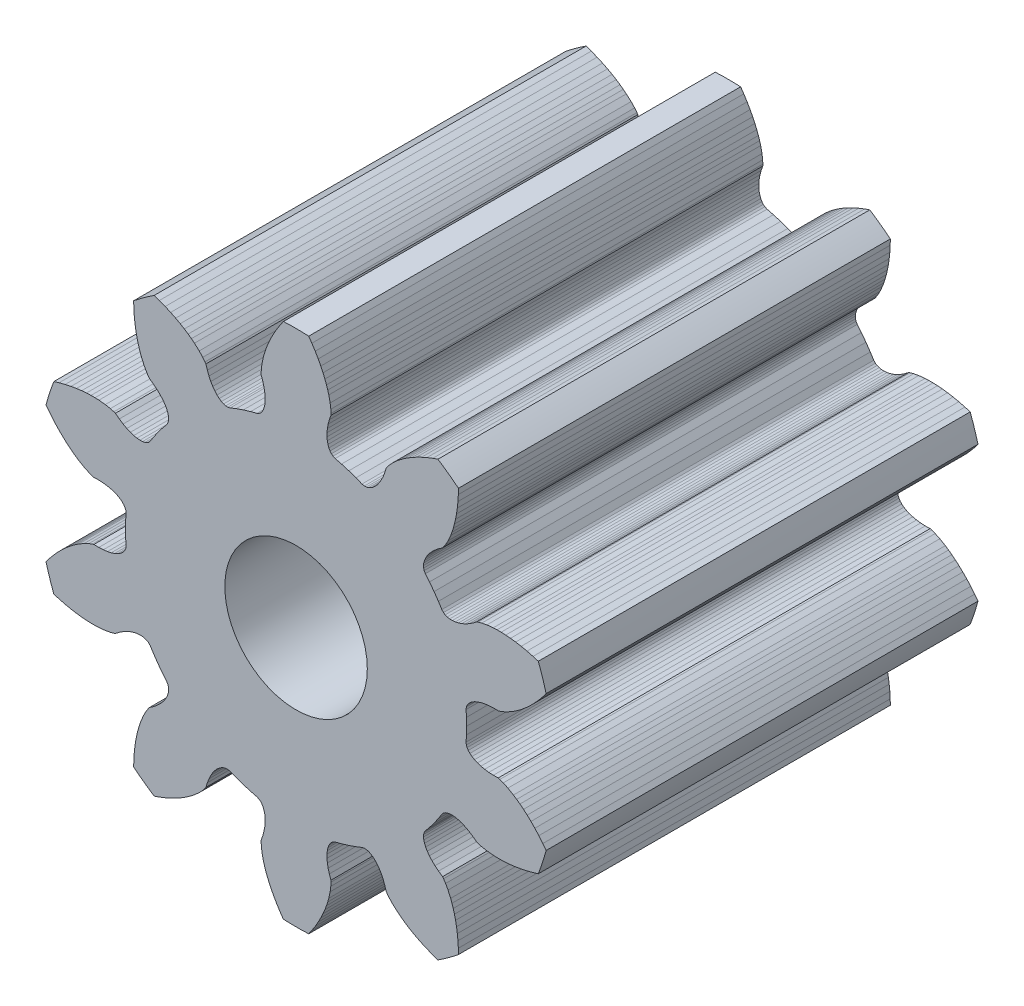
SolidWorks part; units mm, degrees
ref_plane "Front Plane" through (0, 0, 0) normal (0, 0, 1) x (1, 0, 0)
ref_plane "Top Plane" through (0, 0, 0) normal (0, 1, 0) x (1, 0, 0)
ref_plane "Right Plane" through (0, 0, 0) normal (1, 0, 0) x (0, 0, -1)
sketch "Sketch1" plane through (0, 0, 0) normal (0, 0, 1) x (1, 0, 0)
  line L0 (11.2428, -4.5485) -> (11.2517, -4.4039)
  line L1 (11.2517, -4.4039) -> (11.266, -4.2669)
  line L2 (11.266, -4.2669) -> (11.2847, -4.1393)
  line L3 (11.2847, -4.1393) -> (11.3071, -4.0209)
  line L4 (11.3071, -4.0209) -> (11.3325, -3.912)
  line L5 (11.3325, -3.912) -> (11.3608, -3.8103)
  line L6 (11.3608, -3.8103) -> (11.3897, -3.7211)
  line L7 (11.3897, -3.7211) -> (11.4208, -3.6371)
  line L8 (11.4208, -3.6371) -> (11.4807, -3.5016)
  line L9 (11.4807, -3.5016) -> (11.5377, -3.3971)
  line L10 (11.5377, -3.3971) -> (11.5845, -3.3262)
  line L11 (11.5845, -3.3262) -> (11.6076, -3.2964)
  line L12 (11.6076, -3.2964) -> (11.7007, -3.2317)
  line L13 (11.7007, -3.2317) -> (11.7827, -3.1653)
  line L14 (11.7827, -3.1653) -> (11.8533, -3.098)
  line L15 (11.8533, -3.098) -> (11.9128, -3.0308)
  line L16 (11.9128, -3.0308) -> (11.9612, -2.9643)
  line L17 (11.9612, -2.9643) -> (11.9989, -2.8995)
  line L18 (11.9989, -2.8995) -> (12.0259, -2.837)
  line L19 (12.0259, -2.837) -> (12.0426, -2.7776)
  line L20 (12.0426, -2.7776) -> (12.0493, -2.7222)
  line L21 (12.0493, -2.7222) -> (12.0463, -2.6714)
  line L22 (12.0463, -2.6714) -> (12.0342, -2.6259)
  line L23 (12.0342, -2.6259) -> (12.0067, -2.5776)
  line L24 (12.0067, -2.5776) -> (11.9109, -2.4617)
  line L25 (11.9109, -2.4617) -> (11.8044, -2.3217)
  line L26 (11.8044, -2.3217) -> (11.7041, -2.1772)
  line L27 (11.7041, -2.1772) -> (11.6236, -2.0503)
  line L28 (11.6236, -2.0503) -> (11.5861, -2.0092)
  line L29 (11.5861, -2.0092) -> (11.5466, -1.9836)
  line L30 (11.5466, -1.9836) -> (11.4992, -1.9651)
  line L31 (11.4992, -1.9651) -> (11.4444, -1.9543)
  line L32 (11.4444, -1.9543) -> (11.3828, -1.9518)
  line L33 (11.3828, -1.9518) -> (11.315, -1.9582)
  line L34 (11.315, -1.9582) -> (11.2417, -1.974)
  line L35 (11.2417, -1.974) -> (11.1635, -1.9995)
  line L36 (11.1635, -1.9995) -> (11.0812, -2.0353)
  line L37 (11.0812, -2.0353) -> (10.9954, -2.0817)
  line L38 (10.9954, -2.0817) -> (10.907, -2.1391)
  line L39 (10.907, -2.1391) -> (10.8166, -2.2077)
  line L40 (10.8166, -2.2077) -> (10.7811, -2.2204)
  line L41 (10.7811, -2.2204) -> (10.6992, -2.243)
  line L42 (10.6992, -2.243) -> (10.5823, -2.2649)
  line L43 (10.5823, -2.2649) -> (10.4348, -2.2801)
  line L44 (10.4348, -2.2801) -> (10.3453, -2.2837)
  line L45 (10.3453, -2.2837) -> (10.2516, -2.2836)
  line L46 (10.2516, -2.2836) -> (10.1461, -2.2791)
  line L47 (10.1461, -2.2791) -> (10.0348, -2.2696)
  line L48 (10.0348, -2.2696) -> (9.9151, -2.2543)
  line L49 (9.9151, -2.2543) -> (9.7881, -2.2327)
  line L50 (9.7881, -2.2327) -> (9.6533, -2.2039)
  line L51 (9.6533, -2.2039) -> (9.5131, -2.1677)
  line L52 (9.5131, -2.1677) -> (9.3912, -2.1311)
  line L53 (9.2098, -1.5726) -> (9.2868, -1.4714)
  line L54 (9.2868, -1.4714) -> (9.379, -1.3597)
  line L55 (9.379, -1.3597) -> (9.4711, -1.2572)
  line L56 (9.4711, -1.2572) -> (9.5612, -1.165)
  line L57 (9.5612, -1.165) -> (9.649, -1.0823)
  line L58 (9.649, -1.0823) -> (9.7335, -1.0092)
  line L59 (9.7335, -1.0092) -> (9.8162, -0.9435)
  line L60 (9.8162, -0.9435) -> (9.8919, -0.8883)
  line L61 (9.8919, -0.8883) -> (9.9665, -0.8387)
  line L62 (9.9665, -0.8387) -> (10.0947, -0.7642)
  line L63 (10.0947, -0.7642) -> (10.2021, -0.7133)
  line L64 (10.2021, -0.7133) -> (10.2817, -0.6834)
  line L65 (10.2817, -0.6834) -> (10.3179, -0.6728)
  line L66 (10.3179, -0.6728) -> (10.4313, -0.6752)
  line L67 (10.4313, -0.6752) -> (10.5366, -0.6696)
  line L68 (10.5366, -0.6696) -> (10.6333, -0.6568)
  line L69 (10.6333, -0.6568) -> (10.7209, -0.6373)
  line L70 (10.7209, -0.6373) -> (10.7992, -0.612)
  line L71 (10.7992, -0.612) -> (10.8678, -0.5817)
  line L72 (10.8678, -0.5817) -> (10.9263, -0.547)
  line L73 (10.9263, -0.547) -> (10.9747, -0.5088)
  line L74 (10.9747, -0.5088) -> (11.0127, -0.4679)
  line L75 (11.0127, -0.4679) -> (11.0402, -0.4251)
  line L76 (11.0402, -0.4251) -> (11.0571, -0.3811)
  line L77 (11.0571, -0.3811) -> (11.0633, -0.3259)
  line L78 (11.0633, -0.3259) -> (11.0539, -0.1759)
  line L79 (11.0539, -0.1759) -> (11.05, 0)
  line L80 (11.05, 0) -> (11.0539, 0.1759)
  line L81 (11.0539, 0.1759) -> (11.0633, 0.3259)
  line L82 (11.0633, 0.3259) -> (11.0571, 0.3812)
  line L83 (11.0571, 0.3812) -> (11.0402, 0.4251)
  line L84 (11.0402, 0.4251) -> (11.0127, 0.468)
  line L85 (11.0127, 0.468) -> (10.9747, 0.5089)
  line L86 (10.9747, 0.5089) -> (10.9263, 0.5471)
  line L87 (10.9263, 0.5471) -> (10.8678, 0.5817)
  line L88 (10.8678, 0.5817) -> (10.7992, 0.6121)
  line L89 (10.7992, 0.6121) -> (10.7209, 0.6374)
  line L90 (10.7209, 0.6374) -> (10.6333, 0.6568)
  line L91 (10.6333, 0.6568) -> (10.5366, 0.6697)
  line L92 (10.5366, 0.6697) -> (10.4313, 0.6753)
  line L93 (10.4313, 0.6753) -> (10.3179, 0.6729)
  line L94 (10.3179, 0.6729) -> (10.2817, 0.6834)
  line L95 (10.2817, 0.6834) -> (10.2021, 0.7133)
  line L96 (10.2021, 0.7133) -> (10.0947, 0.7643)
  line L97 (10.0947, 0.7643) -> (9.9665, 0.8387)
  line L98 (9.9665, 0.8387) -> (9.8919, 0.8884)
  line L99 (9.8919, 0.8884) -> (9.8162, 0.9436)
  line L100 (9.8162, 0.9436) -> (9.7335, 1.0093)
  line L101 (9.7335, 1.0093) -> (9.649, 1.0824)
  line L102 (9.649, 1.0824) -> (9.5612, 1.165)
  line L103 (9.5612, 1.165) -> (9.4711, 1.2572)
  line L104 (9.4711, 1.2572) -> (9.379, 1.3597)
  line L105 (9.379, 1.3597) -> (9.2868, 1.4714)
  line L106 (9.2868, 1.4714) -> (9.2098, 1.5727)
  line L107 (9.3912, 2.1311) -> (9.5131, 2.1677)
  line L108 (9.5131, 2.1677) -> (9.6533, 2.2039)
  line L109 (9.6533, 2.2039) -> (9.788, 2.2327)
  line L110 (9.788, 2.2327) -> (9.9151, 2.2544)
  line L111 (9.9151, 2.2544) -> (10.0347, 2.2696)
  line L112 (10.0347, 2.2696) -> (10.1461, 2.2791)
  line L113 (10.1461, 2.2791) -> (10.2516, 2.2836)
  line L114 (10.2516, 2.2836) -> (10.3453, 2.2837)
  line L115 (10.3453, 2.2837) -> (10.4348, 2.2801)
  line L116 (10.4348, 2.2801) -> (10.5823, 2.265)
  line L117 (10.5823, 2.265) -> (10.6992, 2.2431)
  line L118 (10.6992, 2.2431) -> (10.7811, 2.2205)
  line L119 (10.7811, 2.2205) -> (10.8166, 2.2078)
  line L120 (10.8166, 2.2078) -> (10.9069, 2.1391)
  line L121 (10.9069, 2.1391) -> (10.9954, 2.0818)
  line L122 (10.9954, 2.0818) -> (11.0812, 2.0353)
  line L123 (11.0812, 2.0353) -> (11.1635, 1.9995)
  line L124 (11.1635, 1.9995) -> (11.2417, 1.974)
  line L125 (11.2417, 1.974) -> (11.315, 1.9583)
  line L126 (11.315, 1.9583) -> (11.3828, 1.9519)
  line L127 (11.3828, 1.9519) -> (11.4444, 1.9543)
  line L128 (11.4444, 1.9543) -> (11.4991, 1.9651)
  line L129 (11.4991, 1.9651) -> (11.5465, 1.9836)
  line L130 (11.5465, 1.9836) -> (11.586, 2.0092)
  line L131 (11.586, 2.0092) -> (11.6235, 2.0503)
  line L132 (11.6235, 2.0503) -> (11.7041, 2.1772)
  line L133 (11.7041, 2.1772) -> (11.8043, 2.3218)
  line L134 (11.8043, 2.3218) -> (11.9109, 2.4618)
  line L135 (11.9109, 2.4618) -> (12.0067, 2.5776)
  line L136 (12.0067, 2.5776) -> (12.0341, 2.626)
  line L137 (12.0341, 2.626) -> (12.0463, 2.6715)
  line L138 (12.0463, 2.6715) -> (12.0492, 2.7223)
  line L139 (12.0492, 2.7223) -> (12.0426, 2.7777)
  line L140 (12.0426, 2.7777) -> (12.0259, 2.837)
  line L141 (12.0259, 2.837) -> (11.9988, 2.8995)
  line L142 (11.9988, 2.8995) -> (11.9612, 2.9643)
  line L143 (11.9612, 2.9643) -> (11.9128, 3.0308)
  line L144 (11.9128, 3.0308) -> (11.8533, 3.0981)
  line L145 (11.8533, 3.0981) -> (11.7826, 3.1653)
  line L146 (11.7826, 3.1653) -> (11.7007, 3.2317)
  line L147 (11.7007, 3.2317) -> (11.6075, 3.2964)
  line L148 (11.6075, 3.2964) -> (11.5845, 3.3262)
  line L149 (11.5845, 3.3262) -> (11.5377, 3.3972)
  line L150 (11.5377, 3.3972) -> (11.4807, 3.5016)
  line L151 (11.4807, 3.5016) -> (11.4208, 3.6372)
  line L152 (11.4208, 3.6372) -> (11.3896, 3.7212)
  line L153 (11.3896, 3.7212) -> (11.3608, 3.8103)
  line L154 (11.3608, 3.8103) -> (11.3325, 3.9121)
  line L155 (11.3325, 3.9121) -> (11.3071, 4.0209)
  line L156 (11.3071, 4.0209) -> (11.2846, 4.1394)
  line L157 (11.2846, 4.1394) -> (11.2659, 4.2669)
  line L158 (11.2659, 4.2669) -> (11.2517, 4.404)
  line L159 (11.2517, 4.404) -> (11.2428, 4.5485)
  line L160 (11.2428, 4.5485) -> (11.2399, 4.6757)
  line L161 (11.715, 5.0209) -> (11.8351, 4.9789)
  line L162 (11.8351, 4.9789) -> (11.9698, 4.9257)
  line L163 (11.9698, 4.9257) -> (12.0958, 4.8698)
  line L164 (12.0958, 4.8698) -> (12.2113, 4.8127)
  line L165 (12.2113, 4.8127) -> (12.3171, 4.7547)
  line L166 (12.3171, 4.7547) -> (12.4127, 4.6969)
  line L167 (12.4127, 4.6969) -> (12.5007, 4.6385)
  line L168 (12.5007, 4.6385) -> (12.5766, 4.5836)
  line L169 (12.5766, 4.5836) -> (12.6469, 4.528)
  line L170 (12.6469, 4.528) -> (12.7573, 4.4291)
  line L171 (12.7573, 4.4291) -> (12.839, 4.3427)
  line L172 (12.839, 4.3427) -> (12.892, 4.2762)
  line L173 (12.892, 4.2762) -> (12.9132, 4.2451)
  line L174 (12.9132, 4.2451) -> (12.946, 4.1364)
  line L175 (12.946, 4.1364) -> (12.9838, 4.038)
  line L176 (12.9838, 4.038) -> (13.0259, 3.9501)
  line L177 (13.0259, 3.9501) -> (13.0715, 3.8727)
  line L178 (13.0715, 3.8727) -> (13.1197, 3.8061)
  line L179 (13.1197, 3.8061) -> (13.1698, 3.7503)
  line L180 (13.1698, 3.7503) -> (13.2209, 3.7053)
  line L181 (13.2209, 3.7053) -> (13.2721, 3.671)
  line L182 (13.2721, 3.671) -> (13.3228, 3.6476)
  line L183 (13.3228, 3.6476) -> (13.372, 3.6347)
  line L184 (13.372, 3.6347) -> (13.419, 3.6322)
  line L185 (13.419, 3.6322) -> (13.4735, 3.6434)
  line L186 (13.4735, 3.6434) -> (13.6133, 3.6987)
  line L187 (13.6133, 3.6987) -> (13.7794, 3.7567)
  line L188 (13.7794, 3.7567) -> (13.9478, 3.8074)
  line L189 (13.9478, 3.8074) -> (14.0934, 3.8448)
  line L190 (14.0934, 3.8448) -> (14.1441, 3.8678)
  line L191 (14.1441, 3.8678) -> (14.1806, 3.8974)
  line L192 (14.1806, 3.8974) -> (14.2129, 3.9368)
  line L193 (14.2129, 3.9368) -> (14.2401, 3.9855)
  line L194 (14.2401, 3.9855) -> (14.2614, 4.0434)
  line L195 (14.2614, 4.0434) -> (14.2763, 4.1098)
  line L196 (14.2763, 4.1098) -> (14.284, 4.1844)
  line L197 (14.284, 4.1844) -> (14.2838, 4.2666)
  line L198 (14.2838, 4.2666) -> (14.2752, 4.356)
  line L199 (14.2752, 4.356) -> (14.2576, 4.4519)
  line L200 (14.2576, 4.4519) -> (14.2304, 4.5538)
  line L201 (14.2304, 4.5538) -> (14.193, 4.6609)
  line L202 (14.193, 4.6609) -> (14.1919, 4.6986)
  line L203 (14.1919, 4.6986) -> (14.1957, 4.7835)
  line L204 (14.1957, 4.7835) -> (14.211, 4.9014)
  line L205 (14.211, 4.9014) -> (14.2422, 5.0463)
  line L206 (14.2422, 5.0463) -> (14.2664, 5.1326)
  line L207 (14.2664, 5.1326) -> (14.2955, 5.2217)
  line L208 (14.2955, 5.2217) -> (14.3324, 5.3207)
  line L209 (14.3324, 5.3207) -> (14.3758, 5.4236)
  line L210 (14.3758, 5.4236) -> (14.4273, 5.5327)
  line L211 (14.4273, 5.5327) -> (14.4871, 5.6468)
  line L212 (14.4871, 5.6468) -> (14.5562, 5.7661)
  line L213 (14.5562, 5.7661) -> (14.6339, 5.8883)
  line L214 (14.6339, 5.8883) -> (14.7064, 5.9928)
  line L215 (15.2936, 5.9928) -> (15.3661, 5.8883)
  line L216 (15.3661, 5.8883) -> (15.4438, 5.7661)
  line L217 (15.4438, 5.7661) -> (15.5128, 5.6468)
  line L218 (15.5128, 5.6468) -> (15.5727, 5.5327)
  line L219 (15.5727, 5.5327) -> (15.6242, 5.4236)
  line L220 (15.6242, 5.4236) -> (15.6676, 5.3207)
  line L221 (15.6676, 5.3207) -> (15.7045, 5.2217)
  line L222 (15.7045, 5.2217) -> (15.7336, 5.1326)
  line L223 (15.7336, 5.1326) -> (15.7578, 5.0464)
  line L224 (15.7578, 5.0464) -> (15.7889, 4.9014)
  line L225 (15.7889, 4.9014) -> (15.8042, 4.7835)
  line L226 (15.8042, 4.7835) -> (15.8081, 4.6986)
  line L227 (15.8081, 4.6986) -> (15.8069, 4.6609)
  line L228 (15.8069, 4.6609) -> (15.7696, 4.5538)
  line L229 (15.7696, 4.5538) -> (15.7424, 4.4519)
  line L230 (15.7424, 4.4519) -> (15.7247, 4.356)
  line L231 (15.7247, 4.356) -> (15.7161, 4.2666)
  line L232 (15.7161, 4.2666) -> (15.716, 4.1844)
  line L233 (15.716, 4.1844) -> (15.7237, 4.1098)
  line L234 (15.7237, 4.1098) -> (15.7385, 4.0434)
  line L235 (15.7385, 4.0434) -> (15.7599, 3.9855)
  line L236 (15.7599, 3.9855) -> (15.7871, 3.9368)
  line L237 (15.7871, 3.9368) -> (15.8193, 3.8974)
  line L238 (15.8193, 3.8974) -> (15.8559, 3.8678)
  line L239 (15.8559, 3.8678) -> (15.9065, 3.8448)
  line L240 (15.9065, 3.8448) -> (16.0521, 3.8074)
  line L241 (16.0521, 3.8074) -> (16.2206, 3.7567)
  line L242 (16.2206, 3.7567) -> (16.3867, 3.6987)
  line L243 (16.3867, 3.6987) -> (16.5264, 3.6434)
  line L244 (16.5264, 3.6434) -> (16.5809, 3.6322)
  line L245 (16.5809, 3.6322) -> (16.6279, 3.6347)
  line L246 (16.6279, 3.6347) -> (16.6772, 3.6476)
  line L247 (16.6772, 3.6476) -> (16.7278, 3.6711)
  line L248 (16.7278, 3.6711) -> (16.7791, 3.7053)
  line L249 (16.7791, 3.7053) -> (16.8301, 3.7503)
  line L250 (16.8301, 3.7503) -> (16.8802, 3.8061)
  line L251 (16.8802, 3.8061) -> (16.9284, 3.8727)
  line L252 (16.9284, 3.8727) -> (16.974, 3.9501)
  line L253 (16.974, 3.9501) -> (17.0161, 4.038)
  line L254 (17.0161, 4.038) -> (17.054, 4.1365)
  line L255 (17.054, 4.1365) -> (17.0867, 4.2451)
  line L256 (17.0867, 4.2451) -> (17.108, 4.2762)
  line L257 (17.108, 4.2762) -> (17.161, 4.3427)
  line L258 (17.161, 4.3427) -> (17.2427, 4.4291)
  line L259 (17.2427, 4.4291) -> (17.3531, 4.528)
  line L260 (17.3531, 4.528) -> (17.4233, 4.5836)
  line L261 (17.4233, 4.5836) -> (17.4992, 4.6385)
  line L262 (17.4992, 4.6385) -> (17.5873, 4.6969)
  line L263 (17.5873, 4.6969) -> (17.6829, 4.7547)
  line L264 (17.6829, 4.7547) -> (17.7886, 4.8127)
  line L265 (17.7886, 4.8127) -> (17.9042, 4.8699)
  line L266 (17.9042, 4.8699) -> (18.0301, 4.9258)
  line L267 (18.0301, 4.9258) -> (18.1648, 4.9789)
  line L268 (18.1648, 4.9789) -> (18.2849, 5.0209)
  line L269 (18.76, 4.6758) -> (18.7572, 4.5486)
  line L270 (18.7572, 4.5486) -> (18.7483, 4.404)
  line L271 (18.7483, 4.404) -> (18.734, 4.2669)
  line L272 (18.734, 4.2669) -> (18.7153, 4.1394)
  line L273 (18.7153, 4.1394) -> (18.6928, 4.0209)
  line L274 (18.6928, 4.0209) -> (18.6675, 3.9121)
  line L275 (18.6675, 3.9121) -> (18.6392, 3.8103)
  line L276 (18.6392, 3.8103) -> (18.6103, 3.7212)
  line L277 (18.6103, 3.7212) -> (18.5792, 3.6372)
  line L278 (18.5792, 3.6372) -> (18.5192, 3.5016)
  line L279 (18.5192, 3.5016) -> (18.4623, 3.3972)
  line L280 (18.4623, 3.3972) -> (18.4155, 3.3263)
  line L281 (18.4155, 3.3263) -> (18.3924, 3.2965)
  line L282 (18.3924, 3.2965) -> (18.2992, 3.2317)
  line L283 (18.2992, 3.2317) -> (18.2173, 3.1653)
  line L284 (18.2173, 3.1653) -> (18.1467, 3.0981)
  line L285 (18.1467, 3.0981) -> (18.0872, 3.0308)
  line L286 (18.0872, 3.0308) -> (18.0387, 2.9644)
  line L287 (18.0387, 2.9644) -> (18.0011, 2.8995)
  line L288 (18.0011, 2.8995) -> (17.9741, 2.837)
  line L289 (17.9741, 2.837) -> (17.9574, 2.7777)
  line L290 (17.9574, 2.7777) -> (17.9507, 2.7223)
  line L291 (17.9507, 2.7223) -> (17.9537, 2.6715)
  line L292 (17.9537, 2.6715) -> (17.9658, 2.626)
  line L293 (17.9658, 2.626) -> (17.9933, 2.5777)
  line L294 (17.9933, 2.5777) -> (18.0891, 2.4618)
  line L295 (18.0891, 2.4618) -> (18.1956, 2.3218)
  line L296 (18.1956, 2.3218) -> (18.2959, 2.1772)
  line L297 (18.2959, 2.1772) -> (18.3764, 2.0503)
  line L298 (18.3764, 2.0503) -> (18.4139, 2.0093)
  line L299 (18.4139, 2.0093) -> (18.4534, 1.9836)
  line L300 (18.4534, 1.9836) -> (18.5008, 1.9651)
  line L301 (18.5008, 1.9651) -> (18.5556, 1.9544)
  line L302 (18.5556, 1.9544) -> (18.6172, 1.9519)
  line L303 (18.6172, 1.9519) -> (18.6849, 1.9583)
  line L304 (18.6849, 1.9583) -> (18.7583, 1.974)
  line L305 (18.7583, 1.974) -> (18.8364, 1.9996)
  line L306 (18.8364, 1.9996) -> (18.9188, 2.0354)
  line L307 (18.9188, 2.0354) -> (19.0046, 2.0818)
  line L308 (19.0046, 2.0818) -> (19.093, 2.1392)
  line L309 (19.093, 2.1392) -> (19.1834, 2.2078)
  line L310 (19.1834, 2.2078) -> (19.2188, 2.2205)
  line L311 (19.2188, 2.2205) -> (19.3008, 2.2431)
  line L312 (19.3008, 2.2431) -> (19.4177, 2.265)
  line L313 (19.4177, 2.265) -> (19.5651, 2.2801)
  line L314 (19.5651, 2.2801) -> (19.6547, 2.2838)
  line L315 (19.6547, 2.2838) -> (19.7484, 2.2837)
  line L316 (19.7484, 2.2837) -> (19.8539, 2.2791)
  line L317 (19.8539, 2.2791) -> (19.9652, 2.2696)
  line L318 (19.9652, 2.2696) -> (20.0848, 2.2544)
  line L319 (20.0848, 2.2544) -> (20.2119, 2.2328)
  line L320 (20.2119, 2.2328) -> (20.3467, 2.204)
  line L321 (20.3467, 2.204) -> (20.4869, 2.1678)
  line L322 (20.4869, 2.1678) -> (20.6088, 2.1312)
  line L323 (20.7902, 1.5727) -> (20.7132, 1.4714)
  line L324 (20.7132, 1.4714) -> (20.621, 1.3598)
  line L325 (20.621, 1.3598) -> (20.5289, 1.2572)
  line L326 (20.5289, 1.2572) -> (20.4388, 1.165)
  line L327 (20.4388, 1.165) -> (20.351, 1.0824)
  line L328 (20.351, 1.0824) -> (20.2665, 1.0093)
  line L329 (20.2665, 1.0093) -> (20.1838, 0.9436)
  line L330 (20.1838, 0.9436) -> (20.108, 0.8884)
  line L331 (20.108, 0.8884) -> (20.0335, 0.8388)
  line L332 (20.0335, 0.8388) -> (19.9053, 0.7643)
  line L333 (19.9053, 0.7643) -> (19.7979, 0.7133)
  line L334 (19.7979, 0.7133) -> (19.7183, 0.6834)
  line L335 (19.7183, 0.6834) -> (19.6821, 0.6729)
  line L336 (19.6821, 0.6729) -> (19.5687, 0.6753)
  line L337 (19.5687, 0.6753) -> (19.4634, 0.6697)
  line L338 (19.4634, 0.6697) -> (19.3667, 0.6568)
  line L339 (19.3667, 0.6568) -> (19.279, 0.6374)
  line L340 (19.279, 0.6374) -> (19.2008, 0.6121)
  line L341 (19.2008, 0.6121) -> (19.1322, 0.5818)
  line L342 (19.1322, 0.5818) -> (19.0736, 0.5471)
  line L343 (19.0736, 0.5471) -> (19.0253, 0.5089)
  line L344 (19.0253, 0.5089) -> (18.9873, 0.468)
  line L345 (18.9873, 0.468) -> (18.9598, 0.4252)
  line L346 (18.9598, 0.4252) -> (18.9429, 0.3812)
  line L347 (18.9429, 0.3812) -> (18.9367, 0.3259)
  line L348 (18.9367, 0.3259) -> (18.9461, 0.1759)
  line L349 (18.9461, 0.1759) -> (18.95, 0)
  line L350 (18.95, 0) -> (18.9461, -0.1758)
  line L351 (18.9461, -0.1758) -> (18.9367, -0.3259)
  line L352 (18.9367, -0.3259) -> (18.9429, -0.3811)
  line L353 (18.9429, -0.3811) -> (18.9598, -0.4251)
  line L354 (18.9598, -0.4251) -> (18.9873, -0.4679)
  line L355 (18.9873, -0.4679) -> (19.0253, -0.5088)
  line L356 (19.0253, -0.5088) -> (19.0736, -0.547)
  line L357 (19.0736, -0.547) -> (19.1322, -0.5817)
  line L358 (19.1322, -0.5817) -> (19.2008, -0.612)
  line L359 (19.2008, -0.612) -> (19.279, -0.6373)
  line L360 (19.279, -0.6373) -> (19.3667, -0.6567)
  line L361 (19.3667, -0.6567) -> (19.4634, -0.6696)
  line L362 (19.4634, -0.6696) -> (19.5687, -0.6752)
  line L363 (19.5687, -0.6752) -> (19.6821, -0.6728)
  line L364 (19.6821, -0.6728) -> (19.7183, -0.6834)
  line L365 (19.7183, -0.6834) -> (19.7979, -0.7132)
  line L366 (19.7979, -0.7132) -> (19.9053, -0.7642)
  line L367 (19.9053, -0.7642) -> (20.0335, -0.8387)
  line L368 (20.0335, -0.8387) -> (20.108, -0.8883)
  line L369 (20.108, -0.8883) -> (20.1838, -0.9435)
  line L370 (20.1838, -0.9435) -> (20.2665, -1.0092)
  line L371 (20.2665, -1.0092) -> (20.351, -1.0823)
  line L372 (20.351, -1.0823) -> (20.4388, -1.1649)
  line L373 (20.4388, -1.1649) -> (20.5289, -1.2571)
  line L374 (20.5289, -1.2571) -> (20.621, -1.3597)
  line L375 (20.621, -1.3597) -> (20.7132, -1.4714)
  line L376 (20.7132, -1.4714) -> (20.7902, -1.5726)
  line L377 (20.6088, -2.131) -> (20.4869, -2.1677)
  line L378 (20.4869, -2.1677) -> (20.3467, -2.2039)
  line L379 (20.3467, -2.2039) -> (20.2119, -2.2327)
  line L380 (20.2119, -2.2327) -> (20.0849, -2.2543)
  line L381 (20.0849, -2.2543) -> (19.9652, -2.2695)
  line L382 (19.9652, -2.2695) -> (19.8539, -2.279)
  line L383 (19.8539, -2.279) -> (19.7484, -2.2836)
  line L384 (19.7484, -2.2836) -> (19.6547, -2.2837)
  line L385 (19.6547, -2.2837) -> (19.5652, -2.28)
  line L386 (19.5652, -2.28) -> (19.4177, -2.2649)
  line L387 (19.4177, -2.2649) -> (19.3008, -2.243)
  line L388 (19.3008, -2.243) -> (19.2189, -2.2204)
  line L389 (19.2189, -2.2204) -> (19.1834, -2.2077)
  line L390 (19.1834, -2.2077) -> (19.093, -2.1391)
  line L391 (19.093, -2.1391) -> (19.0046, -2.0817)
  line L392 (19.0046, -2.0817) -> (18.9188, -2.0353)
  line L393 (18.9188, -2.0353) -> (18.8365, -1.9995)
  line L394 (18.8365, -1.9995) -> (18.7583, -1.9739)
  line L395 (18.7583, -1.9739) -> (18.685, -1.9582)
  line L396 (18.685, -1.9582) -> (18.6172, -1.9518)
  line L397 (18.6172, -1.9518) -> (18.5556, -1.9543)
  line L398 (18.5556, -1.9543) -> (18.5008, -1.965)
  line L399 (18.5008, -1.965) -> (18.4534, -1.9835)
  line L400 (18.4534, -1.9835) -> (18.4139, -2.0092)
  line L401 (18.4139, -2.0092) -> (18.3764, -2.0502)
  line L402 (18.3764, -2.0502) -> (18.2959, -2.1771)
  line L403 (18.2959, -2.1771) -> (18.1956, -2.3217)
  line L404 (18.1956, -2.3217) -> (18.0891, -2.4617)
  line L405 (18.0891, -2.4617) -> (17.9933, -2.5776)
  line L406 (17.9933, -2.5776) -> (17.9658, -2.6259)
  line L407 (17.9658, -2.6259) -> (17.9537, -2.6714)
  line L408 (17.9537, -2.6714) -> (17.9507, -2.7222)
  line L409 (17.9507, -2.7222) -> (17.9574, -2.7776)
  line L410 (17.9574, -2.7776) -> (17.9741, -2.8369)
  line L411 (17.9741, -2.8369) -> (18.0011, -2.8994)
  line L412 (18.0011, -2.8994) -> (18.0387, -2.9643)
  line L413 (18.0387, -2.9643) -> (18.0872, -3.0307)
  line L414 (18.0872, -3.0307) -> (18.1467, -3.098)
  line L415 (18.1467, -3.098) -> (18.2173, -3.1652)
  line L416 (18.2173, -3.1652) -> (18.2992, -3.2316)
  line L417 (18.2992, -3.2316) -> (18.3924, -3.2964)
  line L418 (18.3924, -3.2964) -> (18.4155, -3.3262)
  line L419 (18.4155, -3.3262) -> (18.4623, -3.3971)
  line L420 (18.4623, -3.3971) -> (18.5193, -3.5015)
  line L421 (18.5193, -3.5015) -> (18.5792, -3.6371)
  line L422 (18.5792, -3.6371) -> (18.6103, -3.7211)
  line L423 (18.6103, -3.7211) -> (18.6392, -3.8102)
  line L424 (18.6392, -3.8102) -> (18.6675, -3.912)
  line L425 (18.6675, -3.912) -> (18.6929, -4.0208)
  line L426 (18.6929, -4.0208) -> (18.7153, -4.1393)
  line L427 (18.7153, -4.1393) -> (18.734, -4.2668)
  line L428 (18.734, -4.2668) -> (18.7483, -4.4039)
  line L429 (18.7483, -4.4039) -> (18.7572, -4.5484)
  line L430 (18.7572, -4.5484) -> (18.76, -4.6757)
  line L431 (18.285, -5.0208) -> (18.1648, -4.9788)
  line L432 (18.1648, -4.9788) -> (18.0301, -4.9257)
  line L433 (18.0301, -4.9257) -> (17.9042, -4.8698)
  line L434 (17.9042, -4.8698) -> (17.7886, -4.8126)
  line L435 (17.7886, -4.8126) -> (17.6829, -4.7546)
  line L436 (17.6829, -4.7546) -> (17.5873, -4.6968)
  line L437 (17.5873, -4.6968) -> (17.4992, -4.6385)
  line L438 (17.4992, -4.6385) -> (17.4234, -4.5835)
  line L439 (17.4234, -4.5835) -> (17.3531, -4.5279)
  line L440 (17.3531, -4.5279) -> (17.2427, -4.429)
  line L441 (17.2427, -4.429) -> (17.161, -4.3426)
  line L442 (17.161, -4.3426) -> (17.108, -4.2761)
  line L443 (17.108, -4.2761) -> (17.0868, -4.245)
  line L444 (17.0868, -4.245) -> (17.054, -4.1364)
  line L445 (17.054, -4.1364) -> (17.0161, -4.038)
  line L446 (17.0161, -4.038) -> (16.974, -3.95)
  line L447 (16.974, -3.95) -> (16.9284, -3.8726)
  line L448 (16.9284, -3.8726) -> (16.8802, -3.806)
  line L449 (16.8802, -3.806) -> (16.8302, -3.7502)
  line L450 (16.8302, -3.7502) -> (16.7791, -3.7052)
  line L451 (16.7791, -3.7052) -> (16.7278, -3.671)
  line L452 (16.7278, -3.671) -> (16.6772, -3.6475)
  line L453 (16.6772, -3.6475) -> (16.6279, -3.6346)
  line L454 (16.6279, -3.6346) -> (16.5809, -3.6321)
  line L455 (16.5809, -3.6321) -> (16.5265, -3.6433)
  line L456 (16.5265, -3.6433) -> (16.3867, -3.6986)
  line L457 (16.3867, -3.6986) -> (16.2206, -3.7567)
  line L458 (16.2206, -3.7567) -> (16.0521, -3.8073)
  line L459 (16.0521, -3.8073) -> (15.9066, -3.8447)
  line L460 (15.9066, -3.8447) -> (15.8559, -3.8677)
  line L461 (15.8559, -3.8677) -> (15.8193, -3.8973)
  line L462 (15.8193, -3.8973) -> (15.7871, -3.9367)
  line L463 (15.7871, -3.9367) -> (15.7599, -3.9855)
  line L464 (15.7599, -3.9855) -> (15.7385, -4.0433)
  line L465 (15.7385, -4.0433) -> (15.7237, -4.1097)
  line L466 (15.7237, -4.1097) -> (15.716, -4.1843)
  line L467 (15.716, -4.1843) -> (15.7161, -4.2665)
  line L468 (15.7161, -4.2665) -> (15.7247, -4.3559)
  line L469 (15.7247, -4.3559) -> (15.7424, -4.4518)
  line L470 (15.7424, -4.4518) -> (15.7696, -4.5537)
  line L471 (15.7696, -4.5537) -> (15.8069, -4.6609)
  line L472 (15.8069, -4.6609) -> (15.8081, -4.6985)
  line L473 (15.8081, -4.6985) -> (15.8042, -4.7834)
  line L474 (15.8042, -4.7834) -> (15.789, -4.9014)
  line L475 (15.789, -4.9014) -> (15.7578, -5.0463)
  line L476 (15.7578, -5.0463) -> (15.7336, -5.1325)
  line L477 (15.7336, -5.1325) -> (15.7045, -5.2216)
  line L478 (15.7045, -5.2216) -> (15.6676, -5.3206)
  line L479 (15.6676, -5.3206) -> (15.6242, -5.4235)
  line L480 (15.6242, -5.4235) -> (15.5727, -5.5326)
  line L481 (15.5727, -5.5326) -> (15.5129, -5.6468)
  line L482 (15.5129, -5.6468) -> (15.4438, -5.766)
  line L483 (15.4438, -5.766) -> (15.3661, -5.8882)
  line L484 (15.3661, -5.8882) -> (15.2936, -5.9928)
  line L485 (14.7064, -5.9928) -> (14.6339, -5.8882)
  line L486 (14.6339, -5.8882) -> (14.5561, -5.766)
  line L487 (14.5561, -5.766) -> (14.4871, -5.6468)
  line L488 (14.4871, -5.6468) -> (14.4272, -5.5326)
  line L489 (14.4272, -5.5326) -> (14.3758, -5.4235)
  line L490 (14.3758, -5.4235) -> (14.3324, -5.3206)
  line L491 (14.3324, -5.3206) -> (14.2954, -5.2216)
  line L492 (14.2954, -5.2216) -> (14.2664, -5.1325)
  line L493 (14.2664, -5.1325) -> (14.2422, -5.0463)
  line L494 (14.2422, -5.0463) -> (14.211, -4.9014)
  line L495 (14.211, -4.9014) -> (14.1957, -4.7834)
  line L496 (14.1957, -4.7834) -> (14.1919, -4.6985)
  line L497 (14.1919, -4.6985) -> (14.193, -4.6608)
  line L498 (14.193, -4.6608) -> (14.2304, -4.5537)
  line L499 (14.2304, -4.5537) -> (14.2576, -4.4518)
  line L500 (14.2576, -4.4518) -> (14.2752, -4.3559)
  line L501 (14.2752, -4.3559) -> (14.2838, -4.2665)
  line L502 (14.2838, -4.2665) -> (14.284, -4.1843)
  line L503 (14.284, -4.1843) -> (14.2763, -4.1097)
  line L504 (14.2763, -4.1097) -> (14.2614, -4.0433)
  line L505 (14.2614, -4.0433) -> (14.24, -3.9855)
  line L506 (14.24, -3.9855) -> (14.2129, -3.9367)
  line L507 (14.2129, -3.9367) -> (14.1806, -3.8973)
  line L508 (14.1806, -3.8973) -> (14.144, -3.8677)
  line L509 (14.144, -3.8677) -> (14.0934, -3.8447)
  line L510 (14.0934, -3.8447) -> (13.9478, -3.8073)
  line L511 (13.9478, -3.8073) -> (13.7793, -3.7567)
  line L512 (13.7793, -3.7567) -> (13.6133, -3.6986)
  line L513 (13.6133, -3.6986) -> (13.4735, -3.6433)
  line L514 (13.4735, -3.6433) -> (13.419, -3.6321)
  line L515 (13.419, -3.6321) -> (13.372, -3.6346)
  line L516 (13.372, -3.6346) -> (13.3228, -3.6475)
  line L517 (13.3228, -3.6475) -> (13.2721, -3.671)
  line L518 (13.2721, -3.671) -> (13.2209, -3.7052)
  line L519 (13.2209, -3.7052) -> (13.1698, -3.7502)
  line L520 (13.1698, -3.7502) -> (13.1197, -3.806)
  line L521 (13.1197, -3.806) -> (13.0715, -3.8726)
  line L522 (13.0715, -3.8726) -> (13.0259, -3.95)
  line L523 (13.0259, -3.95) -> (12.9838, -4.038)
  line L524 (12.9838, -4.038) -> (12.946, -4.1364)
  line L525 (12.946, -4.1364) -> (12.9132, -4.245)
  line L526 (12.9132, -4.245) -> (12.892, -4.2761)
  line L527 (12.892, -4.2761) -> (12.839, -4.3426)
  line L528 (12.839, -4.3426) -> (12.7573, -4.429)
  line L529 (12.7573, -4.429) -> (12.6469, -4.5279)
  line L530 (12.6469, -4.5279) -> (12.5766, -4.5835)
  line L531 (12.5766, -4.5835) -> (12.5007, -4.6385)
  line L532 (12.5007, -4.6385) -> (12.4127, -4.6968)
  line L533 (12.4127, -4.6968) -> (12.317, -4.7546)
  line L534 (12.317, -4.7546) -> (12.2113, -4.8126)
  line L535 (12.2113, -4.8126) -> (12.0958, -4.8698)
  line L536 (12.0958, -4.8698) -> (11.9698, -4.9257)
  line L537 (11.9698, -4.9257) -> (11.8351, -4.9788)
  line L538 (11.8351, -4.9788) -> (11.715, -5.0208)
  line L539 (11.24, -4.6757) -> (11.2428, -4.5485)
  line L540 (11.2428, -4.5485) -> (11.2517, -4.4039)
  line L541 (11.2517, -4.4039) -> (11.266, -4.2669)
  line L542 (11.266, -4.2669) -> (11.2847, -4.1393)
  line L543 (11.2847, -4.1393) -> (11.3071, -4.0209)
  line L544 (11.3071, -4.0209) -> (11.3325, -3.912)
  line L545 (11.3325, -3.912) -> (11.3608, -3.8103)
  line L546 (11.3608, -3.8103) -> (11.3897, -3.7211)
  line L547 (11.3897, -3.7211) -> (11.4208, -3.6371)
  line L548 (11.4208, -3.6371) -> (11.4807, -3.5016)
  line L549 (11.4807, -3.5016) -> (11.5377, -3.3971)
  line L550 (11.5377, -3.3971) -> (11.5845, -3.3262)
  line L551 (11.5845, -3.3262) -> (11.6076, -3.2964)
  line L552 (11.6076, -3.2964) -> (11.7007, -3.2317)
  line L553 (11.7007, -3.2317) -> (11.7827, -3.1653)
  line L554 (11.7827, -3.1653) -> (11.8533, -3.098)
  line L555 (11.8533, -3.098) -> (11.9128, -3.0308)
  line L556 (11.9128, -3.0308) -> (11.9612, -2.9643)
  line L557 (11.9612, -2.9643) -> (11.9989, -2.8995)
  line L558 (11.9989, -2.8995) -> (12.0259, -2.837)
  line L559 (12.0259, -2.837) -> (12.0426, -2.7776)
  line L560 (12.0426, -2.7776) -> (12.0493, -2.7222)
  line L561 (12.0493, -2.7222) -> (12.0463, -2.6714)
  line L562 (12.0463, -2.6714) -> (12.0342, -2.6259)
  line L563 (12.0342, -2.6259) -> (12.0067, -2.5776)
  line L564 (12.0067, -2.5776) -> (11.9109, -2.4617)
  line L565 (11.9109, -2.4617) -> (11.8044, -2.3217)
  line L566 (11.8044, -2.3217) -> (11.7041, -2.1772)
  line L567 (11.7041, -2.1772) -> (11.6236, -2.0503)
  line L568 (11.6236, -2.0503) -> (11.5861, -2.0092)
  line L569 (11.5861, -2.0092) -> (11.5466, -1.9836)
  line L570 (11.5466, -1.9836) -> (11.4992, -1.9651)
  line L571 (11.4992, -1.9651) -> (11.4444, -1.9543)
  line L572 (11.4444, -1.9543) -> (11.3828, -1.9518)
  line L573 (11.3828, -1.9518) -> (11.315, -1.9582)
  line L574 (11.315, -1.9582) -> (11.2417, -1.974)
  line L575 (11.2417, -1.974) -> (11.1635, -1.9995)
  line L576 (11.1635, -1.9995) -> (11.0812, -2.0353)
  line L577 (11.0812, -2.0353) -> (10.9954, -2.0817)
  line L578 (10.9954, -2.0817) -> (10.907, -2.1391)
  line L579 (10.907, -2.1391) -> (10.8166, -2.2077)
  line L580 (10.8166, -2.2077) -> (10.7811, -2.2204)
  line L581 (10.7811, -2.2204) -> (10.6992, -2.243)
  line L582 (10.6992, -2.243) -> (10.5823, -2.2649)
  line L583 (10.5823, -2.2649) -> (10.4348, -2.2801)
  line L584 (10.4348, -2.2801) -> (10.3453, -2.2837)
  line L585 (10.3453, -2.2837) -> (10.2516, -2.2836)
  line L586 (10.2516, -2.2836) -> (10.1461, -2.2791)
  line L587 (10.1461, -2.2791) -> (10.0348, -2.2696)
  line L588 (10.0348, -2.2696) -> (9.9151, -2.2543)
  line L589 (9.9151, -2.2543) -> (9.7881, -2.2327)
  line L590 (9.7881, -2.2327) -> (9.6533, -2.2039)
  line L591 (9.6533, -2.2039) -> (9.5131, -2.1677)
  line L592 (9.5131, -2.1677) -> (9.3912, -2.1311)
  line L593 (9.2098, -1.5726) -> (9.2868, -1.4714)
  line L594 (9.2868, -1.4714) -> (9.379, -1.3597)
  line L595 (9.379, -1.3597) -> (9.4711, -1.2572)
  line L596 (9.4711, -1.2572) -> (9.5612, -1.165)
  line L597 (9.5612, -1.165) -> (9.649, -1.0823)
  line L598 (9.649, -1.0823) -> (9.7335, -1.0092)
  line L599 (9.7335, -1.0092) -> (9.8162, -0.9435)
  line L600 (9.8162, -0.9435) -> (9.8919, -0.8883)
  line L601 (9.8919, -0.8883) -> (9.9665, -0.8387)
  line L602 (9.9665, -0.8387) -> (10.0947, -0.7642)
  line L603 (10.0947, -0.7642) -> (10.2021, -0.7133)
  line L604 (10.2021, -0.7133) -> (10.2817, -0.6834)
  line L605 (10.2817, -0.6834) -> (10.3179, -0.6728)
  line L606 (10.3179, -0.6728) -> (10.4313, -0.6752)
  line L607 (10.4313, -0.6752) -> (10.5366, -0.6696)
  line L608 (10.5366, -0.6696) -> (10.6333, -0.6568)
  line L609 (10.6333, -0.6568) -> (10.7209, -0.6373)
  line L610 (10.7209, -0.6373) -> (10.7992, -0.612)
  line L611 (10.7992, -0.612) -> (10.8678, -0.5817)
  line L612 (10.8678, -0.5817) -> (10.9263, -0.547)
  line L613 (10.9263, -0.547) -> (10.9747, -0.5088)
  line L614 (10.9747, -0.5088) -> (11.0127, -0.4679)
  line L615 (11.0127, -0.4679) -> (11.0402, -0.4251)
  line L616 (11.0402, -0.4251) -> (11.0571, -0.3811)
  line L617 (11.0571, -0.3811) -> (11.0633, -0.3259)
  line L618 (11.0633, -0.3259) -> (11.0539, -0.1759)
  line L619 (11.0539, -0.1759) -> (11.05, 0)
  line L620 (11.05, 0) -> (11.0539, 0.1759)
  line L621 (11.0539, 0.1759) -> (11.0633, 0.3259)
  line L622 (11.0633, 0.3259) -> (11.0571, 0.3812)
  line L623 (11.0571, 0.3812) -> (11.0402, 0.4251)
  line L624 (11.0402, 0.4251) -> (11.0127, 0.468)
  line L625 (11.0127, 0.468) -> (10.9747, 0.5089)
  line L626 (10.9747, 0.5089) -> (10.9263, 0.5471)
  line L627 (10.9263, 0.5471) -> (10.8678, 0.5817)
  line L628 (10.8678, 0.5817) -> (10.7992, 0.6121)
  line L629 (10.7992, 0.6121) -> (10.7209, 0.6374)
  line L630 (10.7209, 0.6374) -> (10.6333, 0.6568)
  line L631 (10.6333, 0.6568) -> (10.5366, 0.6697)
  line L632 (10.5366, 0.6697) -> (10.4313, 0.6753)
  line L633 (10.4313, 0.6753) -> (10.3179, 0.6729)
  line L634 (10.3179, 0.6729) -> (10.2817, 0.6834)
  line L635 (10.2817, 0.6834) -> (10.2021, 0.7133)
  line L636 (10.2021, 0.7133) -> (10.0947, 0.7643)
  line L637 (10.0947, 0.7643) -> (9.9665, 0.8387)
  line L638 (9.9665, 0.8387) -> (9.8919, 0.8884)
  line L639 (9.8919, 0.8884) -> (9.8162, 0.9436)
  line L640 (9.8162, 0.9436) -> (9.7335, 1.0093)
  line L641 (9.7335, 1.0093) -> (9.649, 1.0824)
  line L642 (9.649, 1.0824) -> (9.5612, 1.165)
  line L643 (9.5612, 1.165) -> (9.4711, 1.2572)
  line L644 (9.4711, 1.2572) -> (9.379, 1.3597)
  line L645 (9.379, 1.3597) -> (9.2868, 1.4714)
  line L646 (9.2868, 1.4714) -> (9.2098, 1.5727)
  line L647 (9.3912, 2.1311) -> (9.5131, 2.1677)
  line L648 (9.5131, 2.1677) -> (9.6533, 2.2039)
  line L649 (9.6533, 2.2039) -> (9.788, 2.2327)
  line L650 (9.788, 2.2327) -> (9.9151, 2.2544)
  line L651 (9.9151, 2.2544) -> (10.0347, 2.2696)
  line L652 (10.0347, 2.2696) -> (10.1461, 2.2791)
  line L653 (10.1461, 2.2791) -> (10.2516, 2.2836)
  line L654 (10.2516, 2.2836) -> (10.3453, 2.2837)
  line L655 (10.3453, 2.2837) -> (10.4348, 2.2801)
  line L656 (10.4348, 2.2801) -> (10.5823, 2.265)
  line L657 (10.5823, 2.265) -> (10.6992, 2.2431)
  line L658 (10.6992, 2.2431) -> (10.7811, 2.2205)
  line L659 (10.7811, 2.2205) -> (10.8166, 2.2078)
  line L660 (10.8166, 2.2078) -> (10.9069, 2.1391)
  line L661 (10.9069, 2.1391) -> (10.9954, 2.0818)
  line L662 (10.9954, 2.0818) -> (11.0812, 2.0353)
  line L663 (11.0812, 2.0353) -> (11.1635, 1.9995)
  line L664 (11.1635, 1.9995) -> (11.2417, 1.974)
  line L665 (11.2417, 1.974) -> (11.315, 1.9583)
  line L666 (11.315, 1.9583) -> (11.3828, 1.9519)
  line L667 (11.3828, 1.9519) -> (11.4444, 1.9543)
  line L668 (11.4444, 1.9543) -> (11.4991, 1.9651)
  line L669 (11.4991, 1.9651) -> (11.5465, 1.9836)
  line L670 (11.5465, 1.9836) -> (11.586, 2.0092)
  line L671 (11.586, 2.0092) -> (11.6235, 2.0503)
  line L672 (11.6235, 2.0503) -> (11.7041, 2.1772)
  line L673 (11.7041, 2.1772) -> (11.8043, 2.3218)
  line L674 (11.8043, 2.3218) -> (11.9109, 2.4618)
  line L675 (11.9109, 2.4618) -> (12.0067, 2.5776)
  line L676 (12.0067, 2.5776) -> (12.0341, 2.626)
  line L677 (12.0341, 2.626) -> (12.0463, 2.6715)
  line L678 (12.0463, 2.6715) -> (12.0492, 2.7223)
  line L679 (12.0492, 2.7223) -> (12.0426, 2.7777)
  line L680 (12.0426, 2.7777) -> (12.0259, 2.837)
  line L681 (12.0259, 2.837) -> (11.9988, 2.8995)
  line L682 (11.9988, 2.8995) -> (11.9612, 2.9643)
  line L683 (11.9612, 2.9643) -> (11.9128, 3.0308)
  line L684 (11.9128, 3.0308) -> (11.8533, 3.0981)
  line L685 (11.8533, 3.0981) -> (11.7826, 3.1653)
  line L686 (11.7826, 3.1653) -> (11.7007, 3.2317)
  line L687 (11.7007, 3.2317) -> (11.6075, 3.2964)
  line L688 (11.6075, 3.2964) -> (11.5845, 3.3262)
  line L689 (11.5845, 3.3262) -> (11.5377, 3.3972)
  line L690 (11.5377, 3.3972) -> (11.4807, 3.5016)
  line L691 (11.4807, 3.5016) -> (11.4208, 3.6372)
  line L692 (11.4208, 3.6372) -> (11.3896, 3.7212)
  line L693 (11.3896, 3.7212) -> (11.3608, 3.8103)
  line L694 (11.3608, 3.8103) -> (11.3325, 3.9121)
  line L695 (11.3325, 3.9121) -> (11.3071, 4.0209)
  line L696 (11.3071, 4.0209) -> (11.2846, 4.1394)
  line L697 (11.2846, 4.1394) -> (11.2659, 4.2669)
  line L698 (11.2659, 4.2669) -> (11.2517, 4.404)
  line L699 (11.2517, 4.404) -> (11.2428, 4.5485)
  line L700 (11.2428, 4.5485) -> (11.2399, 4.6757)
  line L701 (11.715, 5.0209) -> (11.8351, 4.9789)
  line L702 (11.8351, 4.9789) -> (11.9698, 4.9257)
  line L703 (11.9698, 4.9257) -> (12.0958, 4.8698)
  line L704 (12.0958, 4.8698) -> (12.2113, 4.8127)
  line L705 (12.2113, 4.8127) -> (12.3171, 4.7547)
  line L706 (12.3171, 4.7547) -> (12.4127, 4.6969)
  line L707 (12.4127, 4.6969) -> (12.5007, 4.6385)
  line L708 (12.5007, 4.6385) -> (12.5766, 4.5836)
  line L709 (12.5766, 4.5836) -> (12.6469, 4.528)
  line L710 (12.6469, 4.528) -> (12.7573, 4.4291)
  line L711 (12.7573, 4.4291) -> (12.839, 4.3427)
  line L712 (12.839, 4.3427) -> (12.892, 4.2762)
  line L713 (12.892, 4.2762) -> (12.9132, 4.2451)
  line L714 (12.9132, 4.2451) -> (12.946, 4.1364)
  line L715 (12.946, 4.1364) -> (12.9838, 4.038)
  line L716 (12.9838, 4.038) -> (13.0259, 3.9501)
  line L717 (13.0259, 3.9501) -> (13.0715, 3.8727)
  line L718 (13.0715, 3.8727) -> (13.1197, 3.8061)
  line L719 (13.1197, 3.8061) -> (13.1698, 3.7503)
  line L720 (13.1698, 3.7503) -> (13.2209, 3.7053)
  line L721 (13.2209, 3.7053) -> (13.2721, 3.671)
  line L722 (13.2721, 3.671) -> (13.3228, 3.6476)
  line L723 (13.3228, 3.6476) -> (13.372, 3.6347)
  line L724 (13.372, 3.6347) -> (13.419, 3.6322)
  line L725 (13.419, 3.6322) -> (13.4735, 3.6434)
  line L726 (13.4735, 3.6434) -> (13.6133, 3.6987)
  line L727 (13.6133, 3.6987) -> (13.7794, 3.7567)
  line L728 (13.7794, 3.7567) -> (13.9478, 3.8074)
  line L729 (13.9478, 3.8074) -> (14.0934, 3.8448)
  line L730 (14.0934, 3.8448) -> (14.1441, 3.8678)
  line L731 (14.1441, 3.8678) -> (14.1806, 3.8974)
  line L732 (14.1806, 3.8974) -> (14.2129, 3.9368)
  line L733 (14.2129, 3.9368) -> (14.2401, 3.9855)
  line L734 (14.2401, 3.9855) -> (14.2614, 4.0434)
  line L735 (14.2614, 4.0434) -> (14.2763, 4.1098)
  line L736 (14.2763, 4.1098) -> (14.284, 4.1844)
  line L737 (14.284, 4.1844) -> (14.2838, 4.2666)
  line L738 (14.2838, 4.2666) -> (14.2752, 4.356)
  line L739 (14.2752, 4.356) -> (14.2576, 4.4519)
  line L740 (14.2576, 4.4519) -> (14.2304, 4.5538)
  line L741 (14.2304, 4.5538) -> (14.193, 4.6609)
  line L742 (14.193, 4.6609) -> (14.1919, 4.6986)
  line L743 (14.1919, 4.6986) -> (14.1957, 4.7835)
  line L744 (14.1957, 4.7835) -> (14.211, 4.9014)
  line L745 (14.211, 4.9014) -> (14.2422, 5.0463)
  line L746 (14.2422, 5.0463) -> (14.2664, 5.1326)
  line L747 (14.2664, 5.1326) -> (14.2955, 5.2217)
  line L748 (14.2955, 5.2217) -> (14.3324, 5.3207)
  line L749 (14.3324, 5.3207) -> (14.3758, 5.4236)
  line L750 (14.3758, 5.4236) -> (14.4273, 5.5327)
  line L751 (14.4273, 5.5327) -> (14.4871, 5.6468)
  line L752 (14.4871, 5.6468) -> (14.5562, 5.7661)
  line L753 (14.5562, 5.7661) -> (14.6339, 5.8883)
  line L754 (14.6339, 5.8883) -> (14.7064, 5.9928)
  line L755 (15.2936, 5.9928) -> (15.3661, 5.8883)
  line L756 (15.3661, 5.8883) -> (15.4438, 5.7661)
  line L757 (15.4438, 5.7661) -> (15.5128, 5.6468)
  line L758 (15.5128, 5.6468) -> (15.5727, 5.5327)
  line L759 (15.5727, 5.5327) -> (15.6242, 5.4236)
  line L760 (15.6242, 5.4236) -> (15.6676, 5.3207)
  line L761 (15.6676, 5.3207) -> (15.7045, 5.2217)
  line L762 (15.7045, 5.2217) -> (15.7336, 5.1326)
  line L763 (15.7336, 5.1326) -> (15.7578, 5.0464)
  line L764 (15.7578, 5.0464) -> (15.7889, 4.9014)
  line L765 (15.7889, 4.9014) -> (15.8042, 4.7835)
  line L766 (15.8042, 4.7835) -> (15.8081, 4.6986)
  line L767 (15.8081, 4.6986) -> (15.8069, 4.6609)
  line L768 (15.8069, 4.6609) -> (15.7696, 4.5538)
  line L769 (15.7696, 4.5538) -> (15.7424, 4.4519)
  line L770 (15.7424, 4.4519) -> (15.7247, 4.356)
  line L771 (15.7247, 4.356) -> (15.7161, 4.2666)
  line L772 (15.7161, 4.2666) -> (15.716, 4.1844)
  line L773 (15.716, 4.1844) -> (15.7237, 4.1098)
  line L774 (15.7237, 4.1098) -> (15.7385, 4.0434)
  line L775 (15.7385, 4.0434) -> (15.7599, 3.9855)
  line L776 (15.7599, 3.9855) -> (15.7871, 3.9368)
  line L777 (15.7871, 3.9368) -> (15.8193, 3.8974)
  line L778 (15.8193, 3.8974) -> (15.8559, 3.8678)
  line L779 (15.8559, 3.8678) -> (15.9065, 3.8448)
  line L780 (15.9065, 3.8448) -> (16.0521, 3.8074)
  line L781 (16.0521, 3.8074) -> (16.2206, 3.7567)
  line L782 (16.2206, 3.7567) -> (16.3867, 3.6987)
  line L783 (16.3867, 3.6987) -> (16.5264, 3.6434)
  line L784 (16.5264, 3.6434) -> (16.5809, 3.6322)
  line L785 (16.5809, 3.6322) -> (16.6279, 3.6347)
  line L786 (16.6279, 3.6347) -> (16.6772, 3.6476)
  line L787 (16.6772, 3.6476) -> (16.7278, 3.6711)
  line L788 (16.7278, 3.6711) -> (16.7791, 3.7053)
  line L789 (16.7791, 3.7053) -> (16.8301, 3.7503)
  line L790 (16.8301, 3.7503) -> (16.8802, 3.8061)
  line L791 (16.8802, 3.8061) -> (16.9284, 3.8727)
  line L792 (16.9284, 3.8727) -> (16.974, 3.9501)
  line L793 (16.974, 3.9501) -> (17.0161, 4.038)
  line L794 (17.0161, 4.038) -> (17.054, 4.1365)
  line L795 (17.054, 4.1365) -> (17.0867, 4.2451)
  line L796 (17.0867, 4.2451) -> (17.108, 4.2762)
  line L797 (17.108, 4.2762) -> (17.161, 4.3427)
  line L798 (17.161, 4.3427) -> (17.2427, 4.4291)
  line L799 (17.2427, 4.4291) -> (17.3531, 4.528)
  line L800 (17.3531, 4.528) -> (17.4233, 4.5836)
  line L801 (17.4233, 4.5836) -> (17.4992, 4.6385)
  line L802 (17.4992, 4.6385) -> (17.5873, 4.6969)
  line L803 (17.5873, 4.6969) -> (17.6829, 4.7547)
  line L804 (17.6829, 4.7547) -> (17.7886, 4.8127)
  line L805 (17.7886, 4.8127) -> (17.9042, 4.8699)
  line L806 (17.9042, 4.8699) -> (18.0301, 4.9258)
  line L807 (18.0301, 4.9258) -> (18.1648, 4.9789)
  line L808 (18.1648, 4.9789) -> (18.2849, 5.0209)
  line L809 (18.76, 4.6758) -> (18.7572, 4.5486)
  line L810 (18.7572, 4.5486) -> (18.7483, 4.404)
  line L811 (18.7483, 4.404) -> (18.734, 4.2669)
  line L812 (18.734, 4.2669) -> (18.7153, 4.1394)
  line L813 (18.7153, 4.1394) -> (18.6928, 4.0209)
  line L814 (18.6928, 4.0209) -> (18.6675, 3.9121)
  line L815 (18.6675, 3.9121) -> (18.6392, 3.8103)
  line L816 (18.6392, 3.8103) -> (18.6103, 3.7212)
  line L817 (18.6103, 3.7212) -> (18.5792, 3.6372)
  line L818 (18.5792, 3.6372) -> (18.5192, 3.5016)
  line L819 (18.5192, 3.5016) -> (18.4623, 3.3972)
  line L820 (18.4623, 3.3972) -> (18.4155, 3.3263)
  line L821 (18.4155, 3.3263) -> (18.3924, 3.2965)
  line L822 (18.3924, 3.2965) -> (18.2992, 3.2317)
  line L823 (18.2992, 3.2317) -> (18.2173, 3.1653)
  line L824 (18.2173, 3.1653) -> (18.1467, 3.0981)
  line L825 (18.1467, 3.0981) -> (18.0872, 3.0308)
  line L826 (18.0872, 3.0308) -> (18.0387, 2.9644)
  line L827 (18.0387, 2.9644) -> (18.0011, 2.8995)
  line L828 (18.0011, 2.8995) -> (17.9741, 2.837)
  line L829 (17.9741, 2.837) -> (17.9574, 2.7777)
  line L830 (17.9574, 2.7777) -> (17.9507, 2.7223)
  line L831 (17.9507, 2.7223) -> (17.9537, 2.6715)
  line L832 (17.9537, 2.6715) -> (17.9658, 2.626)
  line L833 (17.9658, 2.626) -> (17.9933, 2.5777)
  line L834 (17.9933, 2.5777) -> (18.0891, 2.4618)
  line L835 (18.0891, 2.4618) -> (18.1956, 2.3218)
  line L836 (18.1956, 2.3218) -> (18.2959, 2.1772)
  line L837 (18.2959, 2.1772) -> (18.3764, 2.0503)
  line L838 (18.3764, 2.0503) -> (18.4139, 2.0093)
  line L839 (18.4139, 2.0093) -> (18.4534, 1.9836)
  line L840 (18.4534, 1.9836) -> (18.5008, 1.9651)
  line L841 (18.5008, 1.9651) -> (18.5556, 1.9544)
  line L842 (18.5556, 1.9544) -> (18.6172, 1.9519)
  line L843 (18.6172, 1.9519) -> (18.6849, 1.9583)
  line L844 (18.6849, 1.9583) -> (18.7583, 1.974)
  line L845 (18.7583, 1.974) -> (18.8364, 1.9996)
  line L846 (18.8364, 1.9996) -> (18.9188, 2.0354)
  line L847 (18.9188, 2.0354) -> (19.0046, 2.0818)
  line L848 (19.0046, 2.0818) -> (19.093, 2.1392)
  line L849 (19.093, 2.1392) -> (19.1834, 2.2078)
  line L850 (19.1834, 2.2078) -> (19.2188, 2.2205)
  line L851 (19.2188, 2.2205) -> (19.3008, 2.2431)
  line L852 (19.3008, 2.2431) -> (19.4177, 2.265)
  line L853 (19.4177, 2.265) -> (19.5651, 2.2801)
  line L854 (19.5651, 2.2801) -> (19.6547, 2.2838)
  line L855 (19.6547, 2.2838) -> (19.7484, 2.2837)
  line L856 (19.7484, 2.2837) -> (19.8539, 2.2791)
  line L857 (19.8539, 2.2791) -> (19.9652, 2.2696)
  line L858 (19.9652, 2.2696) -> (20.0848, 2.2544)
  line L859 (20.0848, 2.2544) -> (20.2119, 2.2328)
  line L860 (20.2119, 2.2328) -> (20.3467, 2.204)
  line L861 (20.3467, 2.204) -> (20.4869, 2.1678)
  line L862 (20.4869, 2.1678) -> (20.6088, 2.1312)
  line L863 (20.7902, 1.5727) -> (20.7132, 1.4714)
  line L864 (20.7132, 1.4714) -> (20.621, 1.3598)
  line L865 (20.621, 1.3598) -> (20.5289, 1.2572)
  line L866 (20.5289, 1.2572) -> (20.4388, 1.165)
  line L867 (20.4388, 1.165) -> (20.351, 1.0824)
  line L868 (20.351, 1.0824) -> (20.2665, 1.0093)
  line L869 (20.2665, 1.0093) -> (20.1838, 0.9436)
  line L870 (20.1838, 0.9436) -> (20.108, 0.8884)
  line L871 (20.108, 0.8884) -> (20.0335, 0.8388)
  line L872 (20.0335, 0.8388) -> (19.9053, 0.7643)
  line L873 (19.9053, 0.7643) -> (19.7979, 0.7133)
  line L874 (19.7979, 0.7133) -> (19.7183, 0.6834)
  line L875 (19.7183, 0.6834) -> (19.6821, 0.6729)
  line L876 (19.6821, 0.6729) -> (19.5687, 0.6753)
  line L877 (19.5687, 0.6753) -> (19.4634, 0.6697)
  line L878 (19.4634, 0.6697) -> (19.3667, 0.6568)
  line L879 (19.3667, 0.6568) -> (19.279, 0.6374)
  line L880 (19.279, 0.6374) -> (19.2008, 0.6121)
  line L881 (19.2008, 0.6121) -> (19.1322, 0.5818)
  line L882 (19.1322, 0.5818) -> (19.0736, 0.5471)
  line L883 (19.0736, 0.5471) -> (19.0253, 0.5089)
  line L884 (19.0253, 0.5089) -> (18.9873, 0.468)
  line L885 (18.9873, 0.468) -> (18.9598, 0.4252)
  line L886 (18.9598, 0.4252) -> (18.9429, 0.3812)
  line L887 (18.9429, 0.3812) -> (18.9367, 0.3259)
  line L888 (18.9367, 0.3259) -> (18.9461, 0.1759)
  line L889 (18.9461, 0.1759) -> (18.95, 0)
  line L890 (18.95, 0) -> (18.9461, -0.1758)
  line L891 (18.9461, -0.1758) -> (18.9367, -0.3259)
  line L892 (18.9367, -0.3259) -> (18.9429, -0.3811)
  line L893 (18.9429, -0.3811) -> (18.9598, -0.4251)
  line L894 (18.9598, -0.4251) -> (18.9873, -0.4679)
  line L895 (18.9873, -0.4679) -> (19.0253, -0.5088)
  line L896 (19.0253, -0.5088) -> (19.0736, -0.547)
  line L897 (19.0736, -0.547) -> (19.1322, -0.5817)
  line L898 (19.1322, -0.5817) -> (19.2008, -0.612)
  line L899 (19.2008, -0.612) -> (19.279, -0.6373)
  line L900 (19.279, -0.6373) -> (19.3667, -0.6567)
  line L901 (19.3667, -0.6567) -> (19.4634, -0.6696)
  line L902 (19.4634, -0.6696) -> (19.5687, -0.6752)
  line L903 (19.5687, -0.6752) -> (19.6821, -0.6728)
  line L904 (19.6821, -0.6728) -> (19.7183, -0.6834)
  line L905 (19.7183, -0.6834) -> (19.7979, -0.7132)
  line L906 (19.7979, -0.7132) -> (19.9053, -0.7642)
  line L907 (19.9053, -0.7642) -> (20.0335, -0.8387)
  line L908 (20.0335, -0.8387) -> (20.108, -0.8883)
  line L909 (20.108, -0.8883) -> (20.1838, -0.9435)
  line L910 (20.1838, -0.9435) -> (20.2665, -1.0092)
  line L911 (20.2665, -1.0092) -> (20.351, -1.0823)
  line L912 (20.351, -1.0823) -> (20.4388, -1.1649)
  line L913 (20.4388, -1.1649) -> (20.5289, -1.2571)
  line L914 (20.5289, -1.2571) -> (20.621, -1.3597)
  line L915 (20.621, -1.3597) -> (20.7132, -1.4714)
  line L916 (20.7132, -1.4714) -> (20.7902, -1.5726)
  line L917 (20.6088, -2.131) -> (20.4869, -2.1677)
  line L918 (20.4869, -2.1677) -> (20.3467, -2.2039)
  line L919 (20.3467, -2.2039) -> (20.2119, -2.2327)
  line L920 (20.2119, -2.2327) -> (20.0849, -2.2543)
  line L921 (20.0849, -2.2543) -> (19.9652, -2.2695)
  line L922 (19.9652, -2.2695) -> (19.8539, -2.279)
  line L923 (19.8539, -2.279) -> (19.7484, -2.2836)
  line L924 (19.7484, -2.2836) -> (19.6547, -2.2837)
  line L925 (19.6547, -2.2837) -> (19.5652, -2.28)
  line L926 (19.5652, -2.28) -> (19.4177, -2.2649)
  line L927 (19.4177, -2.2649) -> (19.3008, -2.243)
  line L928 (19.3008, -2.243) -> (19.2189, -2.2204)
  line L929 (19.2189, -2.2204) -> (19.1834, -2.2077)
  line L930 (19.1834, -2.2077) -> (19.093, -2.1391)
  line L931 (19.093, -2.1391) -> (19.0046, -2.0817)
  line L932 (19.0046, -2.0817) -> (18.9188, -2.0353)
  line L933 (18.9188, -2.0353) -> (18.8365, -1.9995)
  line L934 (18.8365, -1.9995) -> (18.7583, -1.9739)
  line L935 (18.7583, -1.9739) -> (18.685, -1.9582)
  line L936 (18.685, -1.9582) -> (18.6172, -1.9518)
  line L937 (18.6172, -1.9518) -> (18.5556, -1.9543)
  line L938 (18.5556, -1.9543) -> (18.5008, -1.965)
  line L939 (18.5008, -1.965) -> (18.4534, -1.9835)
  line L940 (18.4534, -1.9835) -> (18.4139, -2.0092)
  line L941 (18.4139, -2.0092) -> (18.3764, -2.0502)
  line L942 (18.3764, -2.0502) -> (18.2959, -2.1771)
  line L943 (18.2959, -2.1771) -> (18.1956, -2.3217)
  line L944 (18.1956, -2.3217) -> (18.0891, -2.4617)
  line L945 (18.0891, -2.4617) -> (17.9933, -2.5776)
  line L946 (17.9933, -2.5776) -> (17.9658, -2.6259)
  line L947 (17.9658, -2.6259) -> (17.9537, -2.6714)
  line L948 (17.9537, -2.6714) -> (17.9507, -2.7222)
  line L949 (17.9507, -2.7222) -> (17.9574, -2.7776)
  line L950 (17.9574, -2.7776) -> (17.9741, -2.8369)
  line L951 (17.9741, -2.8369) -> (18.0011, -2.8994)
  line L952 (18.0011, -2.8994) -> (18.0387, -2.9643)
  line L953 (18.0387, -2.9643) -> (18.0872, -3.0307)
  line L954 (18.0872, -3.0307) -> (18.1467, -3.098)
  line L955 (18.1467, -3.098) -> (18.2173, -3.1652)
  line L956 (18.2173, -3.1652) -> (18.2992, -3.2316)
  line L957 (18.2992, -3.2316) -> (18.3924, -3.2964)
  line L958 (18.3924, -3.2964) -> (18.4155, -3.3262)
  line L959 (18.4155, -3.3262) -> (18.4623, -3.3971)
  line L960 (18.4623, -3.3971) -> (18.5193, -3.5015)
  line L961 (18.5193, -3.5015) -> (18.5792, -3.6371)
  line L962 (18.5792, -3.6371) -> (18.6103, -3.7211)
  line L963 (18.6103, -3.7211) -> (18.6392, -3.8102)
  line L964 (18.6392, -3.8102) -> (18.6675, -3.912)
  line L965 (18.6675, -3.912) -> (18.6929, -4.0208)
  line L966 (18.6929, -4.0208) -> (18.7153, -4.1393)
  line L967 (18.7153, -4.1393) -> (18.734, -4.2668)
  line L968 (18.734, -4.2668) -> (18.7483, -4.4039)
  line L969 (18.7483, -4.4039) -> (18.7572, -4.5484)
  line L970 (18.7572, -4.5484) -> (18.76, -4.6757)
  line L971 (18.285, -5.0208) -> (18.1648, -4.9788)
  line L972 (18.1648, -4.9788) -> (18.0301, -4.9257)
  line L973 (18.0301, -4.9257) -> (17.9042, -4.8698)
  line L974 (17.9042, -4.8698) -> (17.7886, -4.8126)
  line L975 (17.7886, -4.8126) -> (17.6829, -4.7546)
  line L976 (17.6829, -4.7546) -> (17.5873, -4.6968)
  line L977 (17.5873, -4.6968) -> (17.4992, -4.6385)
  line L978 (17.4992, -4.6385) -> (17.4234, -4.5835)
  line L979 (17.4234, -4.5835) -> (17.3531, -4.5279)
  line L980 (17.3531, -4.5279) -> (17.2427, -4.429)
  line L981 (17.2427, -4.429) -> (17.161, -4.3426)
  line L982 (17.161, -4.3426) -> (17.108, -4.2761)
  line L983 (17.108, -4.2761) -> (17.0868, -4.245)
  line L984 (17.0868, -4.245) -> (17.054, -4.1364)
  line L985 (17.054, -4.1364) -> (17.0161, -4.038)
  line L986 (17.0161, -4.038) -> (16.974, -3.95)
  line L987 (16.974, -3.95) -> (16.9284, -3.8726)
  line L988 (16.9284, -3.8726) -> (16.8802, -3.806)
  line L989 (16.8802, -3.806) -> (16.8302, -3.7502)
  line L990 (16.8302, -3.7502) -> (16.7791, -3.7052)
  line L991 (16.7791, -3.7052) -> (16.7278, -3.671)
  line L992 (16.7278, -3.671) -> (16.6772, -3.6475)
  line L993 (16.6772, -3.6475) -> (16.6279, -3.6346)
  line L994 (16.6279, -3.6346) -> (16.5809, -3.6321)
  line L995 (16.5809, -3.6321) -> (16.5265, -3.6433)
  line L996 (16.5265, -3.6433) -> (16.3867, -3.6986)
  line L997 (16.3867, -3.6986) -> (16.2206, -3.7567)
  line L998 (16.2206, -3.7567) -> (16.0521, -3.8073)
  line L999 (16.0521, -3.8073) -> (15.9066, -3.8447)
  line L1000 (15.9066, -3.8447) -> (15.8559, -3.8677)
  line L1001 (15.8559, -3.8677) -> (15.8193, -3.8973)
  line L1002 (15.8193, -3.8973) -> (15.7871, -3.9367)
  line L1003 (15.7871, -3.9367) -> (15.7599, -3.9855)
  line L1004 (15.7599, -3.9855) -> (15.7385, -4.0433)
  line L1005 (15.7385, -4.0433) -> (15.7237, -4.1097)
  line L1006 (15.7237, -4.1097) -> (15.716, -4.1843)
  line L1007 (15.716, -4.1843) -> (15.7161, -4.2665)
  line L1008 (15.7161, -4.2665) -> (15.7247, -4.3559)
  line L1009 (15.7247, -4.3559) -> (15.7424, -4.4518)
  line L1010 (15.7424, -4.4518) -> (15.7696, -4.5537)
  line L1011 (15.7696, -4.5537) -> (15.8069, -4.6609)
  line L1012 (15.8069, -4.6609) -> (15.8081, -4.6985)
  line L1013 (15.8081, -4.6985) -> (15.8042, -4.7834)
  line L1014 (15.8042, -4.7834) -> (15.789, -4.9014)
  line L1015 (15.789, -4.9014) -> (15.7578, -5.0463)
  line L1016 (15.7578, -5.0463) -> (15.7336, -5.1325)
  line L1017 (15.7336, -5.1325) -> (15.7045, -5.2216)
  line L1018 (15.7045, -5.2216) -> (15.6676, -5.3206)
  line L1019 (15.6676, -5.3206) -> (15.6242, -5.4235)
  line L1020 (15.6242, -5.4235) -> (15.5727, -5.5326)
  line L1021 (15.5727, -5.5326) -> (15.5129, -5.6468)
  line L1022 (15.5129, -5.6468) -> (15.4438, -5.766)
  line L1023 (15.4438, -5.766) -> (15.3661, -5.8882)
  line L1024 (15.3661, -5.8882) -> (15.2936, -5.9928)
  line L1025 (14.7064, -5.9928) -> (14.6339, -5.8882)
  line L1026 (14.6339, -5.8882) -> (14.5561, -5.766)
  line L1027 (14.5561, -5.766) -> (14.4871, -5.6468)
  line L1028 (14.4871, -5.6468) -> (14.4272, -5.5326)
  line L1029 (14.4272, -5.5326) -> (14.3758, -5.4235)
  line L1030 (14.3758, -5.4235) -> (14.3324, -5.3206)
  line L1031 (14.3324, -5.3206) -> (14.2954, -5.2216)
  line L1032 (14.2954, -5.2216) -> (14.2664, -5.1325)
  line L1033 (14.2664, -5.1325) -> (14.2422, -5.0463)
  line L1034 (14.2422, -5.0463) -> (14.211, -4.9014)
  line L1035 (14.211, -4.9014) -> (14.1957, -4.7834)
  line L1036 (14.1957, -4.7834) -> (14.1919, -4.6985)
  line L1037 (14.1919, -4.6985) -> (14.193, -4.6608)
  line L1038 (14.193, -4.6608) -> (14.2304, -4.5537)
  line L1039 (14.2304, -4.5537) -> (14.2576, -4.4518)
  line L1040 (14.2576, -4.4518) -> (14.2752, -4.3559)
  line L1041 (14.2752, -4.3559) -> (14.2838, -4.2665)
  line L1042 (14.2838, -4.2665) -> (14.284, -4.1843)
  line L1043 (14.284, -4.1843) -> (14.2763, -4.1097)
  line L1044 (14.2763, -4.1097) -> (14.2614, -4.0433)
  line L1045 (14.2614, -4.0433) -> (14.24, -3.9855)
  line L1046 (14.24, -3.9855) -> (14.2129, -3.9367)
  line L1047 (14.2129, -3.9367) -> (14.1806, -3.8973)
  line L1048 (14.1806, -3.8973) -> (14.144, -3.8677)
  line L1049 (14.144, -3.8677) -> (14.0934, -3.8447)
  line L1050 (14.0934, -3.8447) -> (13.9478, -3.8073)
  line L1051 (13.9478, -3.8073) -> (13.7793, -3.7567)
  line L1052 (13.7793, -3.7567) -> (13.6133, -3.6986)
  line L1053 (13.6133, -3.6986) -> (13.4735, -3.6433)
  line L1054 (13.4735, -3.6433) -> (13.419, -3.6321)
  line L1055 (13.419, -3.6321) -> (13.372, -3.6346)
  line L1056 (13.372, -3.6346) -> (13.3228, -3.6475)
  line L1057 (13.3228, -3.6475) -> (13.2721, -3.671)
  line L1058 (13.2721, -3.671) -> (13.2209, -3.7052)
  line L1059 (13.2209, -3.7052) -> (13.1698, -3.7502)
  line L1060 (13.1698, -3.7502) -> (13.1197, -3.806)
  line L1061 (13.1197, -3.806) -> (13.0715, -3.8726)
  line L1062 (13.0715, -3.8726) -> (13.0259, -3.95)
  line L1063 (13.0259, -3.95) -> (12.9838, -4.038)
  line L1064 (12.9838, -4.038) -> (12.946, -4.1364)
  line L1065 (12.946, -4.1364) -> (12.9132, -4.245)
  line L1066 (12.9132, -4.245) -> (12.892, -4.2761)
  line L1067 (12.892, -4.2761) -> (12.839, -4.3426)
  line L1068 (12.839, -4.3426) -> (12.7573, -4.429)
  line L1069 (12.7573, -4.429) -> (12.6469, -4.5279)
  line L1070 (12.6469, -4.5279) -> (12.5766, -4.5835)
  line L1071 (12.5766, -4.5835) -> (12.5007, -4.6385)
  line L1072 (12.5007, -4.6385) -> (12.4127, -4.6968)
  line L1073 (12.4127, -4.6968) -> (12.317, -4.7546)
  line L1074 (12.317, -4.7546) -> (12.2113, -4.8126)
  line L1075 (12.2113, -4.8126) -> (12.0958, -4.8698)
  line L1076 (12.0958, -4.8698) -> (11.9698, -4.9257)
  line L1077 (11.9698, -4.9257) -> (11.8351, -4.9788)
  line L1078 (11.8351, -4.9788) -> (11.715, -5.0208)
  line L1079 (11.24, -4.6757) -> (11.2428, -4.5485)
  arc A0 (9.2098, -1.5726) -> (9.3912, -2.1311) centre (15, 0) ccw
  arc A1 (9.3912, 2.1311) -> (9.2098, 1.5727) centre (15, 0) ccw
  arc A2 (11.715, 5.0209) -> (11.2399, 4.6757) centre (15, 0) ccw
  arc A3 (15.2936, 5.9928) -> (14.7064, 5.9928) centre (15, 0) ccw
  arc A4 (18.76, 4.6758) -> (18.2849, 5.0209) centre (15, 0) ccw
  arc A5 (20.7902, 1.5727) -> (20.6088, 2.1312) centre (15, 0) ccw
  arc A6 (20.6088, -2.131) -> (20.7902, -1.5726) centre (15, 0) ccw
  arc A7 (18.285, -5.0208) -> (18.76, -4.6757) centre (15, 0) ccw
  arc A8 (14.7064, -5.9928) -> (15.2936, -5.9928) centre (15, 0) ccw
  arc A9 (11.24, -4.6757) -> (11.715, -5.0208) centre (15, 0) ccw
  arc A10 (9.2098, -1.5726) -> (9.3912, -2.1311) centre (15, 0) ccw
  arc A11 (9.3912, 2.1311) -> (9.2098, 1.5727) centre (15, 0) ccw
  arc A12 (11.715, 5.0209) -> (11.2399, 4.6757) centre (15, 0) ccw
  arc A13 (15.2936, 5.9928) -> (14.7064, 5.9928) centre (15, 0) ccw
  arc A14 (18.76, 4.6758) -> (18.2849, 5.0209) centre (15, 0) ccw
  arc A15 (20.7902, 1.5727) -> (20.6088, 2.1312) centre (15, 0) ccw
  arc A16 (20.6088, -2.131) -> (20.7902, -1.5726) centre (15, 0) ccw
  arc A17 (18.285, -5.0208) -> (18.76, -4.6757) centre (15, 0) ccw
  arc A18 (14.7064, -5.9928) -> (15.2936, -5.9928) centre (15, 0) ccw
  arc A19 (11.24, -4.6757) -> (11.715, -5.0208) centre (15, 0) ccw
extrude "Boss-Extrude1" add sketch "Sketch1" along normal blind 10 contours L539 A9 L538 L537 L536 L535 L534 L533 L532 L531 L530 L529 L528 L527 L526 L525 L524 L523 L522 L521 L520 L519 L518 L517 L516 L515 L514 L513 L512 L511 L510 L509 L508 L507 L506 L505 L504 L503 L502 L501 L500 L499 L498 L497 L496 L495 L494 L493 L492 L491 L490 region at (15, 0, 0)
sketch "Sketch2" plane through (0, 0, 10) normal (0, 0, 1) x (1, 0, 0)
  circle A0 centre (15, 0) radius 3.95 construction
  point P6 (15, 0)
sketch "Sketch3" plane through (0, 0, 10) normal (0, 0, 1) x (1, 0, 0)
  circle A0 centre (15, 0) radius 1.65
  dimension "D1" = 3.3
extrude "Cut-Extrude1" cut sketch "Sketch3" against normal up to surface (10 mm away) up to face at (15, 0, 0)
